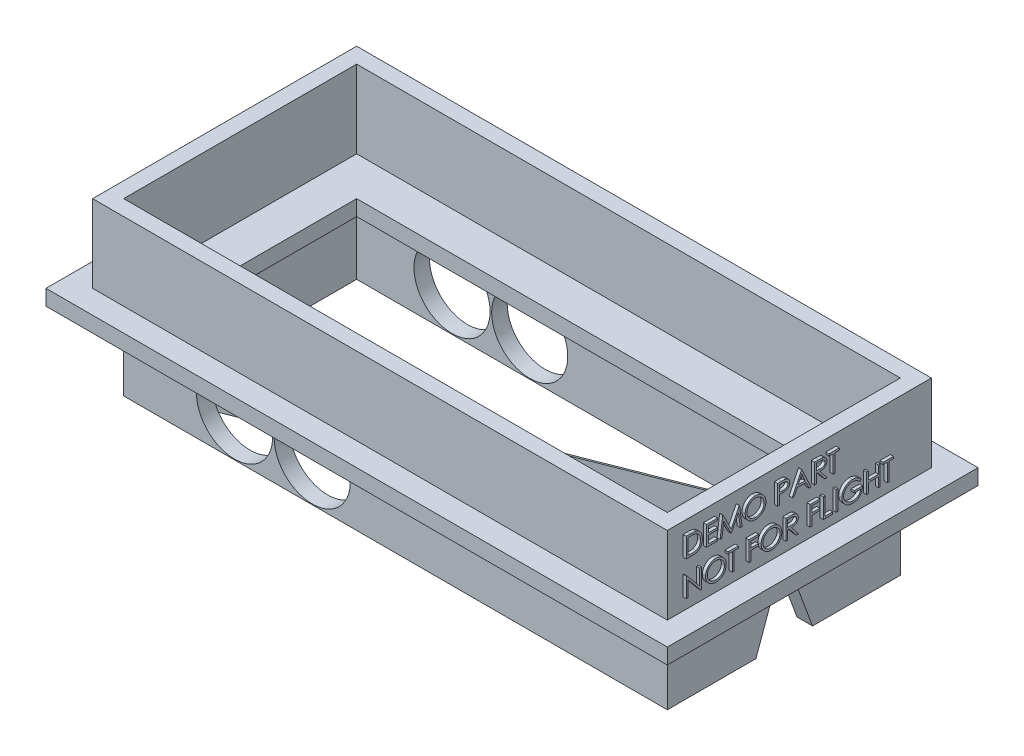
SolidWorks part; units mm, degrees
ref_plane "Front Plane" through (0, 0, 0) normal (0, 0, 1) x (1, 0, 0)
ref_plane "Top Plane" through (0, 0, 0) normal (0, 1, 0) x (1, 0, 0)
ref_plane "Right Plane" through (0, 0, 0) normal (1, 0, 0) x (0, 0, -1)
sketch "Sketch1" plane through (0, 0, 0) normal (0, 1, 0) x (1, 0, 0)
  line L1 (0, 0) -> (330, 0)
  line L2 (0, 0) -> (0, 130)
  line L3 (0, 130) -> (330, 130)
  line L4 (330, 0) -> (330, 130)
  line L5 (-10, -10) -> (340, -10)
  line L6 (-10, -10) -> (-10, 140)
  line L7 (-10, 140) -> (340, 140)
  line L8 (340, -10) -> (340, 140)
  dimension "D1" = 10
  dimension "D2" = 10
  dimension "D3" = 10
  dimension "D4" = 10
  dimension "D5" = 350
  dimension "D6" = 150
extrude "Boss-Extrude1" add sketch "Sketch1" along normal blind 50
sketch "Sketch2" plane through (0, 50, 0) normal (0, 1, 0) x (1, 0, 0)
  line L5 (15, 115) -> (15, 15)
  line L6 (15, 15) -> (315, 15)
  line L7 (315, 15) -> (315, 115)
  line L8 (-35, 165) -> (-35, -35)
  line L9 (-35, -35) -> (365, -35)
  line L10 (365, -35) -> (365, 165)
  line L11 (365, 165) -> (-35, 165)
  line L12 (-35, 165) -> (-35, -35)
  line L13 (-35, -35) -> (365, -35)
  line L14 (365, -35) -> (365, 165)
  line L15 (365, 165) -> (-35, 165)
  line L16 (315, 115) -> (15, 115)
  dimension "D1" = 25
  dimension "D2" = 50
extrude "Boss-Extrude2" add sketch "Sketch2" along normal blind 10
sketch "Sketch3" plane through (0, 60, 0) normal (0, 1, 0) x (1, 0, 0)
  line L4 (-10, 140) -> (-10, -10)
  line L5 (340, 140) -> (-10, 140)
  line L6 (340, -10) -> (340, 140)
  line L7 (-10, -10) -> (340, -10)
  line L8 (-10, 140) -> (-10, -10)
  line L9 (340, 140) -> (-10, 140)
  line L10 (340, -10) -> (340, 140)
  line L11 (-10, -10) -> (340, -10)
  line L16 (-20, 150) -> (-20, -20)
  line L17 (350, 150) -> (-20, 150)
  line L18 (350, -20) -> (350, 150)
  line L19 (-20, -20) -> (350, -20)
  line L20 (-20, 150) -> (-20, -20)
  line L21 (350, 150) -> (-20, 150)
  line L22 (350, -20) -> (350, 150)
  line L23 (-20, -20) -> (350, -20)
  dimension "D1" = 0
  dimension "D2" = 10
extrude "Boss-Extrude3" add sketch "Sketch3" along normal blind 50
sketch "Sketch4" plane through (0, 0, 0) normal (0, -1, 0) x (1, 0, 0)
  line L0 (0.6988, 0) -> (330, -129.2419)
  line L1 (0, 0) -> (330, 0) construction
  line L2 (330, 0) -> (330, -130) construction
  line L3 (329.1944, -130) -> (0, -0.8)
  line L4 (0, -130) -> (0, 0) construction
  line L7 (0, 0) -> (0, -130)
  line L8 (0, -130) -> (330, -130)
  line L9 (330, -130) -> (330, 0)
  line L10 (330, 0) -> (0, 0)
  line L11 (0, 0) -> (0, -0.8)
  line L12 (329.1944, -130) -> (330, -130)
  line L13 (330, -130) -> (330, -129.2419)
  line L14 (0.6988, 0) -> (0, 0)
  point P12 (0, -0.7971)
  point P15 (0.6524, 0)
  point P16 (330, -128.6743)
  point P17 (329.1944, -130)
  dimension "D2" = 1
  dimension "D1" = 0
extrude "Boss-Extrude4" add sketch "Sketch4" against normal blind 25
sketch "Sketch5" plane through (0, 0, -140) normal (0, 0, -1) x (-1, 0, 0)
  circle A0 centre (-61.3968, 24.9582) radius 24.5
  circle A1 centre (-111.3968, 24.9582) radius 24.5
  point P2 (-111.3968, 24.9582)
  dimension "D1" = 49
  dimension "D2" = 49
  dimension "D3" = 50
extrude "Cut-Extrude1" cut sketch "Sketch5" against normal blind 25
extrude "Cut-Extrude2" cut sketch "Sketch5<3>" along normal blind 20 from surface starting at face at (165, 25, 10)
sketch "Sketch5<3>" plane through (0, 0, -140) normal (0, 0, -1) x (-1, 0, 0) same geometry as "Sketch5"
sketch "Sketch6" plane through (340, 0, 0) normal (1, 0, 0) x (0, 0, -1)
  line L0 (47.0504, 0) -> (65, 50)
  line L1 (-10, 0) -> (140, 0) construction
  line L2 (-10, 50) -> (140, 50) construction
  line L3 (65, 50) -> (83.4826, 0)
  line L4 (83.4826, 0) -> (47.0504, 0)
extrude "Cut-Extrude3" cut sketch "Sketch6" against normal blind 20
sketch "Sketch7" plane through (350, 0, 0) normal (1, 0, 0) x (0, 0, -1)
  line L0 (-11.4451, 90.0036) -> (140.8533, 90.0036) construction
  text T0 "DEMO PART\r\nNOT FOR FLIGHT" font "Century Gothic" height in points 48
extrude "Boss-Extrude5" add sketch "Sketch7" along normal blind 2
